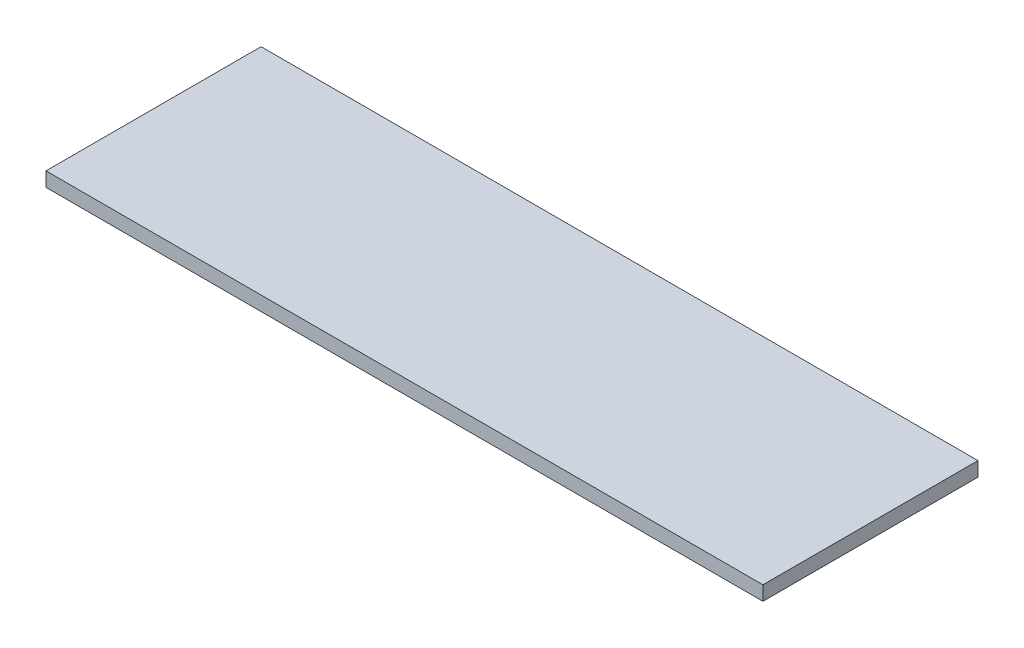
SolidWorks part; units mm, degrees
ref_plane "Front Plane" through (0, 0, 0) normal (0, 0, 1) x (1, 0, 0)
ref_plane "Top Plane" through (0, 0, 0) normal (0, 1, 0) x (1, 0, 0)
ref_plane "Right Plane" through (0, 0, 0) normal (1, 0, 0) x (0, 0, -1)
sketch "Sketch1" plane through (0, 0, 0) normal (1, 0, 0) x (0, 0, -1)
  line L0 (0, 0) -> (0, 25)
  line L1 (0, 0) -> (-2, 0)
  line L2 (-2, 0) -> (-2, 25)
  line L3 (-2, 25) -> (-28, 25)
  line L4 (-28, 25) -> (-28, 27)
  line L5 (-28, 27) -> (2, 27)
  line L6 (2, 27) -> (2, 25)
  line L7 (2, 25) -> (0, 25)
  line L8 (-2, 25) -> (0, 25)
  dimension "D1" = 25
  dimension "D2" = 2
  dimension "D3" = 26
  dimension "D4" = 30
extrude "Boss-Extrude1" add sketch "Sketch1" along normal mid plane 10 contours L8 L2 L1 L0 | L3 L8 L7 L6 L5 L4 region at (0, 12.5, 1) region at (0, 26, 13)
extrude "Boss-Extrude2" add sketch "Sketch1<3>" along normal mid plane 100 contours L3 L8 L7 L6 L5 L4 region at (0, 26, 13)
sketch "Sketch1<3>" plane through (0, 0, 0) normal (1, 0, 0) x (0, 0, -1) same geometry as "Sketch1"
sketch "Sketch2" plane through (0, 0, 0) normal (0, 0, -1) x (-1, 0, 0)
  circle A0 centre (0, 5) radius 1.5
  dimension "D2" = 3
  dimension "D1" = 5
extrude "Cut-Extrude1" cut sketch "Sketch2" against normal through all both and the other way through all
